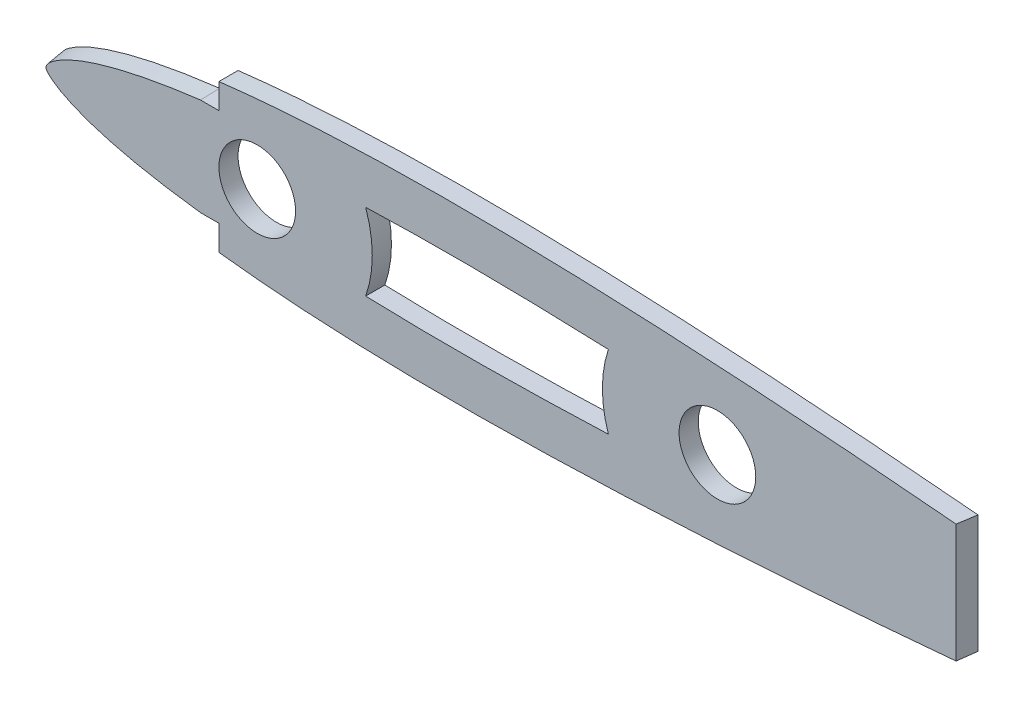
SolidWorks part; units mm, degrees
material "Balsa"
ref_plane "Front Plane" through (0, 0, 0) normal (0, 0, 1) x (1, 0, 0)
ref_plane "Top Plane" through (0, 0, 0) normal (0, 1, 0) x (1, 0, 0)
ref_plane "Right Plane" through (0, 0, 0) normal (1, 0, 0) x (0, 0, -1)
curve "Curve1"
  spline degree 3 poles (237.2261, -0.4007, 0) (237.2261, 0.4007, 0) (236.427, 0.3028, 0) (235.4144, 0.5879, 0) (233.5575, 0.7641, 0) (231.056, 1.1422, 0) (227.8336, 1.5641, 0) (223.9477, 2.0841, 0) (219.4082, 2.6719, 0) (214.2482, 3.3264, 0) (208.4977, 4.0361, 0) (202.1927, 4.7913, 0) (195.3719, 5.5827, 0) (188.0775, 6.3996, 0) (180.3543, 7.2319, 0) (172.25, 8.0693, 0) (163.8146, 8.9011, 0) (155.1002, 9.7155, 0) (146.1603, 10.5018, 0) (137.0502, 11.2469, 0) (127.8259, 11.9387, 0) (118.5443, 12.5643, 0) (109.2626, 13.1106, 0) (100.038, 13.5638, 0) (90.9275, 13.9119, 0) (81.9868, 14.1435, 0) (73.2714, 14.2472, 0) (64.8346, 14.2148, 0) (56.7287, 14.0402, 0) (49.0033, 13.7188, 0) (41.7062, 13.2499, 0) (34.8822, 12.6348, 0) (28.5729, 11.8783, 0) (22.8169, 10.9869, 0) (17.649, 9.97, 0) (13.0996, 8.8388, 0) (9.1945, 7.6047, 0) (5.9535, 6.2789, 0) (3.3869, 4.8705, 0) (1.4988, 3.3767, 0) (0.2895, 1.7614, 0) (-0.1349, 0, 0) (0.2895, -1.7614, 0) (1.4988, -3.3767, 0) (3.3869, -4.8705, 0) (5.9535, -6.2789, 0) (9.1945, -7.6047, 0) (13.0996, -8.8388, 0) (17.649, -9.97, 0) (22.8169, -10.9869, 0) (28.5729, -11.8783, 0) (34.8822, -12.6348, 0) (41.7062, -13.2499, 0) (49.0033, -13.7188, 0) (56.7287, -14.0402, 0) (64.8346, -14.2148, 0) (73.2714, -14.2472, 0) (81.9868, -14.1435, 0) (90.9275, -13.9119, 0) (100.038, -13.5638, 0) (109.2626, -13.1106, 0) (118.5443, -12.5643, 0) (127.8259, -11.9387, 0) (137.0502, -11.2469, 0) (146.1603, -10.5018, 0) (155.1002, -9.7155, 0) (163.8146, -8.9011, 0) (172.25, -8.0693, 0) (180.3543, -7.2319, 0) (188.0775, -6.3996, 0) (195.3719, -5.5827, 0) (202.1927, -4.7913, 0) (208.4977, -4.0361, 0) (214.2482, -3.3264, 0) (219.4082, -2.6719, 0) (223.9477, -2.0841, 0) (227.8336, -1.5641, 0) (231.056, -1.1422, 0) (233.5575, -0.7641, 0) (235.4144, -0.5879, 0) (236.427, -0.3028, 0) (237.2261, -0.4007, 0) (237.2261, 0.4007, 0) (236.427, 0.3028, 0) knots -0.004279 -0.001997 -0.001234 0 0.000762 0.003045 0.006832 0.012101 0.018818 0.026939 0.036415 0.047185 0.05918 0.072328 0.086544 0.101741 0.117823 0.134691 0.15224 0.170361 0.188941 0.207865 0.227016 0.246276 0.265525 0.284645 0.30352 0.322035 0.340078 0.357543 0.374325 0.39033 0.405464 0.419644 0.432793 0.444844 0.455738 0.465429 0.473886 0.481102 0.487102 0.491975 0.495931 0.499383 0.502835 0.50679 0.511664 0.517664 0.524879 0.533337 0.543028 0.553922 0.565972 0.579122 0.593302 0.608436 0.62444 0.641223 0.658687 0.676731 0.695245 0.714121 0.733241 0.75249 0.77175 0.7909 0.809825 0.828404 0.846525 0.864074 0.880942 0.897025 0.912222 0.926438 0.939585 0.951581 0.962351 0.971826 0.979948 0.986664 0.991933 0.995721 0.998003 0.998766 1 1.000762 1.003045 1.006832 periodic
sketch "Sketch1" plane through (0, 0, 0) normal (0, 0, 1) x (1, 0, 0)
  spline S0 degree 3 poles (237.2261, -0.4007) (237.2261, 0.4007) (236.427, 0.3028) (235.4144, 0.5879) (233.5575, 0.7641) (231.056, 1.1422) (227.8336, 1.5641) (223.9477, 2.0841) (219.4082, 2.6719) (214.2482, 3.3264) (208.4977, 4.0361) (202.1927, 4.7913) (195.3719, 5.5827) (188.0775, 6.3996) (180.3543, 7.2319) (172.25, 8.0693) (163.8146, 8.9011) (155.1002, 9.7155) (146.1603, 10.5018) (137.0502, 11.2469) (127.8259, 11.9387) (118.5443, 12.5643) (109.2626, 13.1106) (100.038, 13.5638) (90.9275, 13.9119) (81.9868, 14.1435) (73.2714, 14.2472) (64.8346, 14.2148) (56.7287, 14.0402) (49.0033, 13.7188) (41.7062, 13.2499) (34.8822, 12.6348) (28.5729, 11.8783) (22.8169, 10.9869) (17.649, 9.97) (13.0996, 8.8388) (9.1945, 7.6047) (5.9535, 6.2789) (3.3869, 4.8705) (1.4988, 3.3767) (0.2895, 1.7614) (-0.1349, 0) (0.2895, -1.7614) (1.4988, -3.3767) (3.3869, -4.8705) (5.9535, -6.2789) (9.1945, -7.6047) (13.0996, -8.8388) (17.649, -9.97) (22.8169, -10.9869) (28.5729, -11.8783) (34.8822, -12.6348) (41.7062, -13.2499) (49.0033, -13.7188) (56.7287, -14.0402) (64.8346, -14.2148) (73.2714, -14.2472) (81.9868, -14.1435) (90.9275, -13.9119) (100.038, -13.5638) (109.2626, -13.1106) (118.5443, -12.5643) (127.8259, -11.9387) (137.0502, -11.2469) (146.1603, -10.5018) (155.1002, -9.7155) (163.8146, -8.9011) (172.25, -8.0693) (180.3543, -7.2319) (188.0775, -6.3996) (195.3719, -5.5827) (202.1927, -4.7913) (208.4977, -4.0361) (214.2482, -3.3264) (219.4082, -2.6719) (223.9477, -2.0841) (227.8336, -1.5641) (231.056, -1.1422) (233.5575, -0.7641) (235.4144, -0.5879) (236.427, -0.3028) (237.2261, -0.4007) (237.2261, 0.4007) (236.427, 0.3028) knots -0.004279 -0.001997 -0.001234 0 0.000762 0.003045 0.006832 0.012101 0.018818 0.026939 0.036415 0.047185 0.05918 0.072328 0.086544 0.101741 0.117823 0.134691 0.15224 0.170361 0.188941 0.207865 0.227016 0.246276 0.265525 0.284645 0.30352 0.322035 0.340078 0.357543 0.374325 0.39033 0.405464 0.419644 0.432793 0.444844 0.455738 0.465429 0.473886 0.481102 0.487102 0.491975 0.495931 0.499383 0.502835 0.50679 0.511664 0.517664 0.524879 0.533337 0.543028 0.553922 0.565972 0.579122 0.593302 0.608436 0.62444 0.641223 0.658687 0.676731 0.695245 0.714121 0.733241 0.75249 0.77175 0.7909 0.809825 0.828404 0.846525 0.864074 0.880942 0.897025 0.912222 0.926438 0.939585 0.951581 0.962351 0.971826 0.979948 0.986664 0.991933 0.995721 0.998003 0.998766 1 1.000762 1.003045 1.006832 only from (237.0836, 0.2987) to (237.0836, 0.2987) construction
  spline S1 degree 3 poles (237.2261, -0.4007) (237.2261, 0.4007) (236.427, 0.3028) (235.4144, 0.5879) (233.5575, 0.7641) (231.056, 1.1422) (227.8336, 1.5641) (223.9477, 2.0841) (219.4082, 2.6719) (214.2482, 3.3264) (208.4977, 4.0361) (202.1927, 4.7913) (195.3719, 5.5827) (188.0775, 6.3996) (180.3543, 7.2319) (172.25, 8.0693) (163.8146, 8.9011) (155.1002, 9.7155) (146.1603, 10.5018) (137.0502, 11.2469) (127.8259, 11.9387) (118.5443, 12.5643) (109.2626, 13.1106) (100.038, 13.5638) (90.9275, 13.9119) (81.9868, 14.1435) (73.2714, 14.2472) (64.8346, 14.2148) (56.7287, 14.0402) (49.0033, 13.7188) (41.7062, 13.2499) (34.8822, 12.6348) (28.5729, 11.8783) (22.8169, 10.9869) (17.649, 9.97) (13.0996, 8.8388) (9.1945, 7.6047) (5.9535, 6.2789) (3.3869, 4.8705) (1.4988, 3.3767) (0.2895, 1.7614) (-0.1349, 0) (0.2895, -1.7614) (1.4988, -3.3767) (3.3869, -4.8705) (5.9535, -6.2789) (9.1945, -7.6047) (13.0996, -8.8388) (17.649, -9.97) (22.8169, -10.9869) (28.5729, -11.8783) (34.8822, -12.6348) (41.7062, -13.2499) (49.0033, -13.7188) (56.7287, -14.0402) (64.8346, -14.2148) (73.2714, -14.2472) (81.9868, -14.1435) (90.9275, -13.9119) (100.038, -13.5638) (109.2626, -13.1106) (118.5443, -12.5643) (127.8259, -11.9387) (137.0502, -11.2469) (146.1603, -10.5018) (155.1002, -9.7155) (163.8146, -8.9011) (172.25, -8.0693) (180.3543, -7.2319) (188.0775, -6.3996) (195.3719, -5.5827) (202.1927, -4.7913) (208.4977, -4.0361) (214.2482, -3.3264) (219.4082, -2.6719) (223.9477, -2.0841) (227.8336, -1.5641) (231.056, -1.1422) (233.5575, -0.7641) (235.4144, -0.5879) (236.427, -0.3028) (237.2261, -0.4007) (237.2261, 0.4007) (236.427, 0.3028) knots -0.004279 -0.001997 -0.001234 0 0.000762 0.003045 0.006832 0.012101 0.018818 0.026939 0.036415 0.047185 0.05918 0.072328 0.086544 0.101741 0.117823 0.134691 0.15224 0.170361 0.188941 0.207865 0.227016 0.246276 0.265525 0.284645 0.30352 0.322035 0.340078 0.357543 0.374325 0.39033 0.405464 0.419644 0.432793 0.444844 0.455738 0.465429 0.473886 0.481102 0.487102 0.491975 0.495931 0.499383 0.502835 0.50679 0.511664 0.517664 0.524879 0.533337 0.543028 0.553922 0.565972 0.579122 0.593302 0.608436 0.62444 0.641223 0.658687 0.676731 0.695245 0.714121 0.733241 0.75249 0.77175 0.7909 0.809825 0.828404 0.846525 0.864074 0.880942 0.897025 0.912222 0.926438 0.939585 0.951581 0.962351 0.971826 0.979948 0.986664 0.991933 0.995721 0.998003 0.998766 1 1.000762 1.003045 1.006832 only from (237.0836, 0.2987) to (237.0836, 0.2987)
extrude "Boss-Extrude1" add sketch "Sketch1" along normal blind 3.175
sketch "Sketch2" plane through (0, 0, 3.175) normal (0, 0, 1) x (1, 0, 0)
  circle A0 centre (38.1, 0) radius 6.35
  circle A1 centre (114.3, 0) radius 6.35
  dimension "D1" = 12.7
  dimension "D2" = 12.7
  dimension "D3" = 0
  dimension "D4" = 0
  dimension "D5" = 38.1
  dimension "D6" = 114.3
extrude "Cut-Extrude1" cut sketch "Sketch2" against normal blind 3.175
sketch "Sketch3" plane through (0, 0, 0) normal (0, 1, 0) x (1, 0, 0)
  line L2 (154.2743, 0) -> (153.8276, -3.175)
  line L4 (237.1905, 0) -> (0, 0) construction
  line L5 (237.1905, 0) -> (154.2743, 0)
  line L8 (237.1905, -3.175) -> (237.1905, 0) construction
  line L9 (237.1905, -3.175) -> (237.1905, 0)
  line L11 (153.8276, -3.175) -> (237.1905, -3.175)
extrude "Cut-Extrude2" cut sketch "Sketch3" against normal through all both and the other way through all
sketch "Sketch5" plane through (0, 0, 0) normal (0, 0, -1) x (-1, 0, 0)
  line L0 (-31.75, -11.7736) -> (-31.75, -8.173)
  line L1 (-31.75, -11.7736) -> (-31.75, -8.173)
  line L2 (-28.702, -8.173) -> (-31.75, -8.173)
  line L3 (-28.702, -8.173) -> (-31.75, -8.173)
  line L4 (-31.75, 8.173) -> (-31.75, 11.7736)
  line L5 (-31.75, 8.173) -> (-31.75, 11.7736)
  line L6 (-31.75, 8.173) -> (-28.702, 8.173)
  line L7 (-31.75, 8.173) -> (-28.702, 8.173)
  line L8 (-31.75, 11.7736) -> (-31.75, 14.8587)
  line L9 (-31.75, 14.8587) -> (1.816, 11.7736)
  line L10 (1.816, 11.7736) -> (0.4549, -12.7446)
  line L11 (0.4549, -12.7446) -> (-31.75, -15.9024)
  line L12 (-31.75, -15.9024) -> (-31.75, -11.7736)
  spline S0 degree 3 poles (1922.9425, 444.9353) (-218.2575, -47.1523) (-117.0988, 20.5169) (-24.7906, 7.6566) (-22.844, 7.3585) (-20.908, 7.0325) (-18.9871, 6.677) (-17.0833, 6.2879) (-15.1978, 5.8612) (-13.6488, 5.4708) (-12.4253, 5.1351) (-11.518, 4.8708) (-10.6222, 4.5928) (-9.7397, 4.3001) (-8.8718, 3.9915) (-8.0239, 3.6675) (-7.2012, 3.3286) (-6.4085, 2.974) (-5.6532, 2.6043) (-4.9405, 2.2165) (-4.2792, 1.8093) (-3.6908, 1.4005) (-3.283, 1.0721) (-3.0134, 0.8108) (-2.845, 0.6177) (-2.711, 0.4266) (-2.6274, 0.2633) (-2.5818, 0.118) (-2.5689, 0) (-2.5818, -0.118) (-2.6274, -0.2633) (-2.711, -0.4266) (-2.845, -0.6177) (-3.0134, -0.8108) (-3.2832, -1.0721) (-3.6907, -1.4004) (-4.2792, -1.8093) (-4.9405, -2.2165) (-5.6532, -2.6043) (-6.4085, -2.974) (-7.2012, -3.3286) (-8.0238, -3.6675) (-8.8718, -3.9915) (-9.7397, -4.3001) (-10.6222, -4.5928) (-11.518, -4.8708) (-12.4253, -5.1351) (-13.6488, -5.4708) (-15.1978, -5.8612) (-17.0833, -6.2879) (-18.9871, -6.677) (-20.908, -7.0325) (-22.844, -7.3585) (-24.7905, -7.6566) (-116.1394, -20.3835) (-216.2202, 45.7211) (1930.2923, -410.6134) knots -4.334106 -4.334106 -4.334106 -4.334106 0.03125 0.0625 0.09375 0.125 0.15625 0.1875 0.21875 0.25 0.265625 0.28125 0.296875 0.3125 0.328125 0.34375 0.359375 0.375 0.390625 0.40625 0.421875 0.4375 0.453125 0.460938 0.46875 0.476562 0.484375 0.492188 0.5 0.507812 0.515625 0.523438 0.53125 0.539062 0.546875 0.5625 0.578125 0.59375 0.609375 0.625 0.640625 0.65625 0.671875 0.6875 0.703125 0.71875 0.734375 0.75 0.78125 0.8125 0.84375 0.875 0.90625 0.9375 0.96875 5.287985 5.287985 5.287985 5.287985 only from (-28.702, 8.173) to (-28.702, -8.173)
  spline S1 degree 3 poles (-28.702, 8.173) (-28.0499, 8.0942) (-26.745, 7.9289) (-24.7906, 7.6566) (-22.844, 7.3585) (-20.908, 7.0325) (-18.9871, 6.677) (-17.0833, 6.2879) (-15.1978, 5.8612) (-13.6488, 5.4708) (-12.4253, 5.1351) (-11.518, 4.8708) (-10.6222, 4.5928) (-9.7397, 4.3001) (-8.8718, 3.9915) (-8.0239, 3.6675) (-7.2012, 3.3286) (-6.4085, 2.974) (-5.6532, 2.6043) (-4.9405, 2.2165) (-4.2792, 1.8093) (-3.6908, 1.4005) (-3.283, 1.0721) (-3.0134, 0.8108) (-2.845, 0.6177) (-2.711, 0.4266) (-2.6274, 0.2633) (-2.5818, 0.118) (-2.5689, 0) (-2.5818, -0.118) (-2.6274, -0.2633) (-2.711, -0.4266) (-2.845, -0.6177) (-3.0134, -0.8108) (-3.2832, -1.0721) (-3.6907, -1.4004) (-4.2792, -1.8093) (-4.9405, -2.2165) (-5.6532, -2.6043) (-6.4085, -2.974) (-7.2012, -3.3286) (-8.0238, -3.6675) (-8.8718, -3.9915) (-9.7397, -4.3001) (-10.6222, -4.5928) (-11.518, -4.8708) (-12.4253, -5.1351) (-13.6488, -5.4708) (-15.1978, -5.8612) (-17.0833, -6.2879) (-18.9871, -6.677) (-20.908, -7.0325) (-22.844, -7.3585) (-24.7905, -7.6566) (-26.745, -7.9289) (-28.0499, -8.0942) (-28.702, -8.173) knots 0 0 0 0 0.03125 0.0625 0.09375 0.125 0.15625 0.1875 0.21875 0.25 0.265625 0.28125 0.296875 0.3125 0.328125 0.34375 0.359375 0.375 0.390625 0.40625 0.421875 0.4375 0.453125 0.460938 0.46875 0.476562 0.484375 0.492188 0.5 0.507812 0.515625 0.523438 0.53125 0.539062 0.546875 0.5625 0.578125 0.59375 0.609375 0.625 0.640625 0.65625 0.671875 0.6875 0.703125 0.71875 0.734375 0.75 0.78125 0.8125 0.84375 0.875 0.90625 0.9375 0.96875 1 1 1 1
sketch "Sketch6" plane through (0, 0, 3.175) normal (0, 0, 1) x (1, 0, 0)
  line L0 (31.75, 8.0764) -> (31.75, 11.6833)
  line L1 (31.75, 8.0764) -> (31.75, 11.6833)
  line L2 (28.702, -8.0764) -> (31.75, -8.0764)
  line L3 (28.702, -8.0764) -> (31.75, -8.0764)
  line L4 (31.75, -11.6833) -> (31.75, -8.0764)
  line L5 (31.75, -11.6833) -> (31.75, -8.0764)
  line L6 (31.75, 8.0764) -> (28.702, 8.0764)
  line L7 (31.75, 8.0764) -> (28.702, 8.0764)
  line L8 (31.75, 11.6833) -> (31.75, 18.3959)
  line L9 (31.75, 18.3959) -> (-8.9984, 14.1869)
  line L10 (-8.9984, 14.1869) -> (-8.0322, -19.0612)
  line L11 (-8.0322, -19.0612) -> (31.75, -17.6645)
  line L12 (31.75, -17.6645) -> (31.75, -11.6833)
  spline S0 degree 3 poles (-1926.103, 430.7131) (214.6665, -46.0059) (115.3645, 20.4087) (24.8632, 7.5596) (22.9529, 7.2618) (21.0532, 6.9366) (19.1688, 6.5823) (17.3014, 6.1949) (15.4524, 5.7705) (13.9338, 5.3826) (12.7348, 5.0493) (11.8458, 4.787) (10.9683, 4.5113) (10.1041, 4.2211) (9.2546, 3.9154) (8.4251, 3.5946) (7.6208, 3.2593) (6.8465, 2.9089) (6.1095, 2.544) (5.4151, 2.1619) (4.7717, 1.7612) (4.2006, 1.3602) (3.8064, 1.0398) (3.5462, 0.7856) (3.3839, 0.5981) (3.2548, 0.4126) (3.1742, 0.2543) (3.1304, 0.1138) (3.118, 0) (3.1304, -0.1138) (3.1742, -0.2543) (3.2548, -0.4126) (3.3839, -0.5981) (3.5462, -0.7856) (3.8065, -1.0398) (4.2006, -1.3601) (4.7718, -1.7612) (5.4151, -2.1619) (6.1095, -2.5441) (6.8464, -2.9089) (7.6208, -3.2593) (8.425, -3.5945) (9.2546, -3.9154) (10.1041, -4.2211) (10.9683, -4.5113) (11.8458, -4.787) (12.7348, -5.0493) (13.9339, -5.3826) (15.4524, -5.7705) (17.3014, -6.1949) (19.1688, -6.5823) (21.0532, -6.9366) (22.9529, -7.2618) (24.8631, -7.5596) (114.4091, -20.2734) (212.6358, 44.5789) (-1933.1174, -396.4449) knots -4.329585 -4.329585 -4.329585 -4.329585 0.03125 0.0625 0.09375 0.125 0.15625 0.1875 0.21875 0.25 0.265625 0.28125 0.296875 0.3125 0.328125 0.34375 0.359375 0.375 0.390625 0.40625 0.421875 0.4375 0.453125 0.460938 0.46875 0.476562 0.484375 0.492188 0.5 0.507812 0.515625 0.523438 0.53125 0.539062 0.546875 0.5625 0.578125 0.59375 0.609375 0.625 0.640625 0.65625 0.671875 0.6875 0.703125 0.71875 0.734375 0.75 0.78125 0.8125 0.84375 0.875 0.90625 0.9375 0.96875 5.282783 5.282783 5.282783 5.282783 only from (28.702, 8.0764) to (28.702, -8.0764)
  spline S1 degree 3 poles (28.702, 8.0764) (28.062, 7.9974) (26.7814, 7.8319) (24.8632, 7.5596) (22.9529, 7.2618) (21.0532, 6.9366) (19.1688, 6.5823) (17.3014, 6.1949) (15.4524, 5.7705) (13.9338, 5.3826) (12.7348, 5.0493) (11.8458, 4.787) (10.9683, 4.5113) (10.1041, 4.2211) (9.2546, 3.9154) (8.4251, 3.5946) (7.6208, 3.2593) (6.8465, 2.9089) (6.1095, 2.544) (5.4151, 2.1619) (4.7717, 1.7612) (4.2006, 1.3602) (3.8064, 1.0398) (3.5462, 0.7856) (3.3839, 0.5981) (3.2548, 0.4126) (3.1742, 0.2543) (3.1304, 0.1138) (3.118, 0) (3.1304, -0.1138) (3.1742, -0.2543) (3.2548, -0.4126) (3.3839, -0.5981) (3.5462, -0.7856) (3.8065, -1.0398) (4.2006, -1.3601) (4.7718, -1.7612) (5.4151, -2.1619) (6.1095, -2.5441) (6.8464, -2.9089) (7.6208, -3.2593) (8.425, -3.5945) (9.2546, -3.9154) (10.1041, -4.2211) (10.9683, -4.5113) (11.8458, -4.787) (12.7348, -5.0493) (13.9339, -5.3826) (15.4524, -5.7705) (17.3014, -6.1949) (19.1688, -6.5823) (21.0532, -6.9366) (22.9529, -7.2618) (24.8631, -7.5596) (26.7813, -7.8319) (28.062, -7.9974) (28.702, -8.0764) knots 0 0 0 0 0.03125 0.0625 0.09375 0.125 0.15625 0.1875 0.21875 0.25 0.265625 0.28125 0.296875 0.3125 0.328125 0.34375 0.359375 0.375 0.390625 0.40625 0.421875 0.4375 0.453125 0.460938 0.46875 0.476562 0.484375 0.492188 0.5 0.507812 0.515625 0.523438 0.53125 0.539062 0.546875 0.5625 0.578125 0.59375 0.609375 0.625 0.640625 0.65625 0.671875 0.6875 0.703125 0.71875 0.734375 0.75 0.78125 0.8125 0.84375 0.875 0.90625 0.9375 0.96875 1 1 1 1
loft "Cut-Loft1" cut profiles "Sketch6", "Sketch5" connector at (31.75, 18.3959, 3.175) connector at (31.75, 14.8587, 0)
sketch "Sketch7" plane through (0, 0, 3.175) normal (0, 0, 1) x (1, 0, 0)
  line L2 (146.2076, -2.8409) -> (146.2076, 2.8409)
  arc A3 (56.0542, -6.3678) -> (56.0542, 6.3678) centre (38.1, 0) ccw
  arc A4 (96.2458, 6.0785) -> (96.2458, -6.0785) centre (114.3, 0) ccw
  spline S7 degree 3 poles (96.2458, 6.0785) (93.8614, 6.1723) (91.4778, 6.2553) (84.3446, 6.4683) (79.5987, 6.5623) (70.1215, 6.6291) (65.3899, 6.6022) (59.1317, 6.4625) (57.592, 6.4198) (56.0542, 6.3678) knots 0.43731 0.43731 0.43731 0.43731 0.5 0.5 0.625 0.625 0.75 0.75 0.790836 0.790836 0.790836 0.790836
  spline S8 degree 3 poles (1861.9599, 2350.2628) (-219.6941, 152.781) (-109.3199, 7.6586) (41.9044, -5.6026) (44.2362, -5.7741) (51.2512, -6.2083) (55.9556, -6.3916) (65.3899, -6.6022) (70.1215, -6.6291) (79.5987, -6.5623) (84.3446, -6.4683) (98.5966, -6.0428) (108.1137, -5.5705) (568.8842, 23.3346) (1029.7944, 331.9743) (829.5056, -2718.7599) knots -3.947268 -3.947268 -3.947268 -3.947268 0.0625 0.0625 0.125 0.125 0.25 0.25 0.375 0.375 0.5 0.5 0.75 0.75 12.597732 12.597732 12.597732 12.597732 only from (32.6569, -4.6849) to (146.2076, -2.8409)
  spline S9 degree 3 poles (829.5102, 2718.6907) (1029.7875, -331.9696) (568.8808, -23.3344) (108.1137, 5.5705) (98.5966, 6.0428) (84.3446, 6.4683) (79.5987, 6.5623) (70.1215, 6.6291) (65.3899, 6.6022) (55.9556, 6.3916) (51.2512, 6.2083) (44.2362, 5.7741) (41.9044, 5.6026) (-109.3184, -7.6584) (-219.6918, -152.7781) (1861.8973, -2350.1967) knots -11.597643 -11.597643 -11.597643 -11.597643 0.25 0.25 0.5 0.5 0.625 0.625 0.75 0.75 0.875 0.875 0.9375 0.9375 4.947227 4.947227 4.947227 4.947227 only from (146.2076, 2.8409) to (32.6569, 4.6849)
  spline S10 degree 3 poles (56.0542, -6.3678) (57.592, -6.4198) (59.1317, -6.4625) (65.3899, -6.6022) (70.1215, -6.6291) (79.5987, -6.5623) (84.3446, -6.4683) (91.4778, -6.2553) (93.8614, -6.1723) (96.2458, -6.0785) knots 0.209164 0.209164 0.209164 0.209164 0.25 0.25 0.375 0.375 0.5 0.5 0.56269 0.56269 0.56269 0.56269
  dimension "D1" = 7.62
extrude "Cut-Extrude3" cut sketch "Sketch7" against normal blind 7.62
